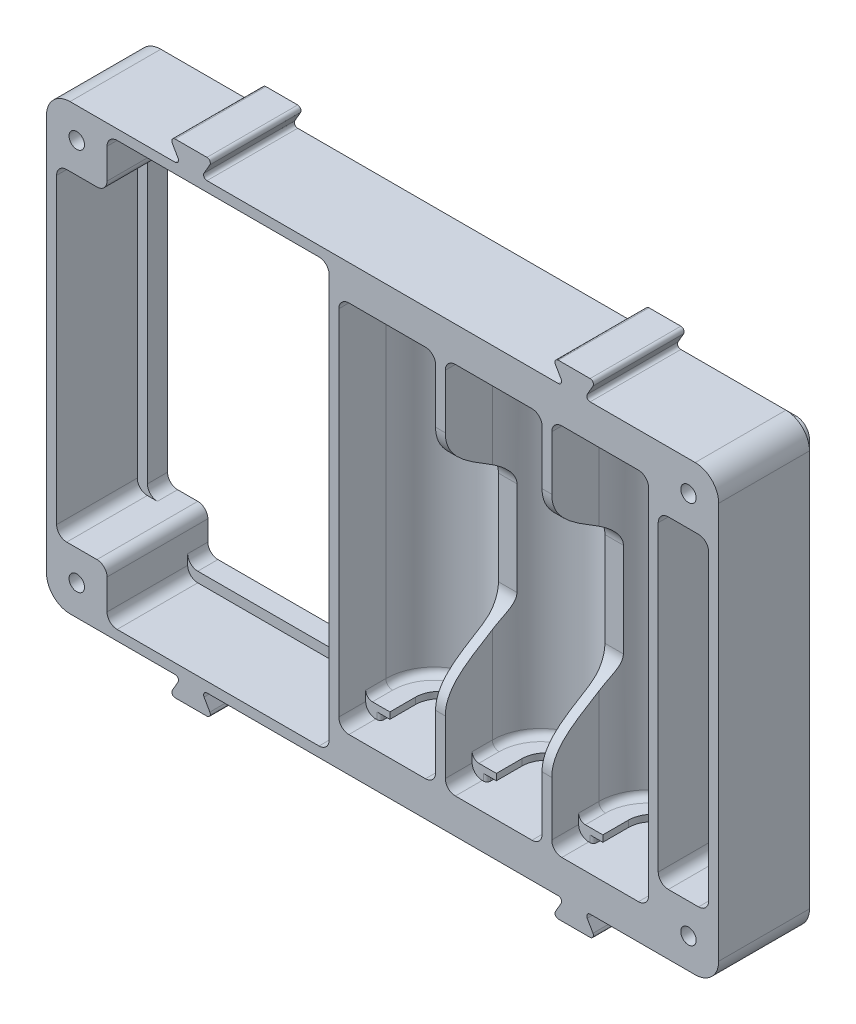
SolidWorks part; units mm, degrees
material "ABS"
ref_plane "Front Plane" through (0, 0, 0) normal (0, 0, 1) x (1, 0, 0)
ref_plane "Top Plane" through (0, 0, 0) normal (0, 1, 0) x (1, 0, 0)
ref_plane "Right Plane" through (0, 0, 0) normal (1, 0, 0) x (0, 0, -1)
sketch "Sketch1" plane through (0, 0, 0) normal (0, 1, 0) x (1, 0, 0)
  line L0 (-24.48, 0) -> (24.48, 0)
  line L1 (0, 0) -> (0, -8) construction
  line L2 (-5.4908, -0.8) -> (5.6475, -0.8) construction
  line L3 (7, -12.013) -> (7, -2.4204) construction
  line L4 (8.84, -11.8066) -> (8.84, -1.8587) construction
  line L5 (0, -8) -> (15.84, -8) construction
  line L6 (7.2, -8) -> (7.2, -15)
  line L7 (8.64, -8) -> (8.64, -15)
  line L8 (8.64, -15) -> (23.04, -15) construction
  line L9 (8.64, -15) -> (7.2, -15)
  line L10 (-1.7094, -15) -> (7.2, -15) construction
  line L11 (15.84, -8) -> (23.04, -8) construction
  line L12 (23.04, -15) -> (23.04, -8)
  line L13 (23.04, -15) -> (24.48, -15)
  line L14 (24.48, -15) -> (24.48, 0)
  line L15 (-24.48, -15) -> (-24.48, 0)
  line L16 (-23.04, -15) -> (-24.48, -15)
  line L17 (-23.04, -15) -> (-23.04, -8)
  line L18 (-8.64, -8) -> (-8.64, -15)
  line L19 (-8.64, -15) -> (-7.2, -15)
  line L20 (-7.2, -8) -> (-7.2, -15)
  circle A0 centre (0, -8) radius 7 construction
  arc A1 (-7.2, -8) -> (7.2, -8) centre (0, -8) cw
  circle A2 centre (15.84, -8) radius 7 construction
  arc A3 (8.64, -8) -> (23.04, -8) centre (15.84, -8) cw
  arc A4 (-8.64, -8) -> (-23.04, -8) centre (-15.84, -8) ccw
  dimension "D1" = 14
  dimension "D2" = 0.2
  dimension "D3" = 0.8
  dimension "D4" = 1.44
  dimension "D5" = 15
  dimension "D6" = 15.84
extrude "Boss-Extrude1" add sketch "Sketch1" along normal blind 27.8
sketch "Sketch2" plane through (0, 27.8, 0) normal (0, -1, 0) x (1, 0, 0)
  line L1 (-24.48, 15) -> (24.48, 15)
  line L2 (-24.48, 15) -> (-24.48, 0)
  line L3 (-24.48, 0) -> (24.48, 0)
  line L4 (24.48, 15) -> (24.48, 0)
extrude "Boss-Extrude2" add sketch "Sketch2" against normal blind 1.44
ref_plane "Plane1" through (-15.84, 0, 0) normal (1, 0, 0) x (0, 0, -1)
ref_plane "Plane3" through (15.84, 0, 0) normal (1, 0, 0) x (0, 0, -1)
sketch "Sketch6" plane through (0, 0, 0) normal (1, 0, 0) x (0, 0, -1)
  line L0 (-5, 0) -> (-15, 0)
  line L1 (-15, 0) -> (0, 0) construction
  line L2 (-15, 0) -> (-15, 18.24)
  line L3 (-15, 29.24) -> (-15, 0) construction
  line L4 (-5, 0) -> (-5, 7)
  line L5 (0, 29.24) -> (0, 0) construction
  line L6 (0, 29.24) -> (-15, 29.24) construction
  spline S0 degree 3 poles (-15, 18.24) (-15, 12.24) (-5, 11) (-5, 7) knots 0 0 0 0 1 1 1 1
  dimension "D4" = 12
  dimension "D5" = 18
  dimension "D1" = 7
  dimension "D2" = 5
  dimension "D3" = 11
extrude "Cut-Extrude2" cut sketch "Sketch6" against normal blind 15 and the other way blind 15
sketch "Sketch3" plane through (0, 27.8, 0) normal (0, -1, 0) x (1, 0, 0)
  line L0 (-10.34, 11) -> (-8.64, 11)
  line L1 (-8.64, 8) -> (-8.64, 15) construction
  line L2 (-8.64, 11) -> (-8.64, 0)
  line L3 (24.48, 0) -> (-24.48, 0) construction
  line L4 (-8.64, 0) -> (-23.04, 0)
  line L6 (-20.34, 2.9) -> (-11.34, 2.9)
  line L7 (-10.84, 3.4) -> (-10.84, 10.5)
  line L8 (-15.84, 15) -> (-15.84, 0) construction
  line L9 (-8.64, 15) -> (-23.04, 15) construction
  line L19 (-23.04, 11) -> (-23.04, 0)
  line L20 (-21.34, 11) -> (-23.04, 11)
  line L21 (-20.84, 3.4) -> (-20.84, 10.5)
  arc A1 (-11.34, 2.9) -> (-10.84, 3.4) centre (-11.34, 3.4) ccw
  arc A4 (-10.34, 11) -> (-10.84, 10.5) centre (-10.34, 10.5) ccw
  arc A6 (-20.34, 2.9) -> (-20.84, 3.4) centre (-20.34, 3.4) cw
  arc A7 (-21.34, 11) -> (-20.84, 10.5) centre (-21.34, 10.5) cw
  dimension "D6" = 0.5
  dimension "D7" = 0.5
  dimension "D1" = 5
  dimension "D2" = 11
  dimension "D3" = 2.9
extrude "Inner" add sketch "Sketch3" along normal blind 1
sketch "Sketch4" plane through (0, 26.8, 0) normal (0, -1, 0) x (1, 0, 0)
  line L1 (-8.64, 8) -> (-8.64, 15) construction
  line L2 (-8.64, 11) -> (-8.64, 0)
  line L3 (24.48, 0) -> (-24.48, 0) construction
  line L4 (-8.64, 0) -> (-23.04, 0)
  line L5 (-23.04, 0) -> (-23.04, 11)
  line L6 (-8.64, 11) -> (-10.34, 11) construction
  line L7 (-23.04, 11) -> (-19.44, 11)
  line L8 (-19.44, 11) -> (-19.44, 7.2)
  line L10 (-12.24, 7.2) -> (-12.24, 11)
  line L11 (-12.24, 11) -> (-8.64, 11)
  arc A0 (-19.44, 7.2) -> (-12.24, 7.2) centre (-15.84, 7.2) ccw
  dimension "D1" = 3.6
  dimension "D2" = 3.8
extrude "Boss-Extrude4" add sketch "Sketch4" along normal blind 0.96
sketch "Sketch5" plane through (0, 0, 15) normal (0, 0, 1) x (1, 0, 0)
  line L0 (-8.64, 27.8) -> (-23.04, 27.8) construction
  line L1 (-17.54, 27.8) -> (-14.14, 27.8)
  line L2 (-17.54, 27.8) -> (-17.54, 27.3)
  line L3 (-17.54, 27.3) -> (-14.14, 27.3)
  line L4 (-14.14, 27.8) -> (-14.14, 27.3)
  point P10 (-15.84, 27.8)
  dimension "D1" = 0.5
  dimension "D2" = 3.4
extrude "Cut-Extrude1" cut sketch "Sketch5" against normal through all
sketch "Sketch10" plane through (0, 0, 0) normal (0, 0, 1) x (1, 0, 0)
  line L0 (-24.48, 29.24) -> (24.48, 29.24) construction
  line L1 (-14.14, 27.3) -> (-17.54, 27.3)
  line L2 (-14.14, 27.3) -> (-14.14, 29.24)
  line L3 (-14.14, 29.24) -> (-17.54, 29.24)
  line L4 (-17.54, 27.3) -> (-17.54, 29.24)
extrude "Cut-Extrude6" cut sketch "Sketch10" along normal blind 0.6
mirror "Mirror1" about plane through (0, 0, 0) normal (1, 0, 0) of "Cut-Extrude6", "Inner", "Boss-Extrude4", "Cut-Extrude1"
ref_plane "Plane2" through (-7.92, 0, 0) normal (1, 0, 0) x (0, 0, -1)
mirror "Mirror2" about plane through (-7.92, 0, 0) normal (1, 0, 0) of "Cut-Extrude6", "Inner", "Boss-Extrude4", "Cut-Extrude1"
fillet "Fillet2" radius 1.5 6 edges at (-8.64, 27.8, 13) (-23.04, 27.8, 13) (23.04, 27.8, 13) (-7.2, 27.8, 13) (7.2, 27.8, 13) (8.64, 27.8, 13)
fillet "Fillet3" radius 1 9 edges at (-8.64, 25.84, 9.5) (-15.84, 25.84, 0.8) (-23.04, 25.84, 9.5) (23.04, 25.84, 9.5) (8.64, 25.84, 9.5) (7.2, 25.84, 9.5) (-7.2, 25.84, 9.5) (15.84, 25.84, 0.8) (0, 25.84, 0.8)
fillet "Fillet4" [suppressed] radius 2.94
mirror "Mirror4" about plane through (0, 0, 0) normal (0, 1, 0) of bodies 108 110
sketch "Sketch12" [suppressed] plane through (0, 0, 0) normal (0, 0, -1) x (-1, 0, 0)
  line L0 (-7.92, 7) -> (-7.92, 25) construction
  line L1 (-6.5452, 7) -> (-9.2948, 7) construction
  line L2 (7.92, 7) -> (7.92, 18) construction
  line L3 (9.2948, 7) -> (6.5452, 7) construction
  line L4 (7.92, 7) -> (7.92, -15) construction
  line L5 (-7.92, 7) -> (-7.92, -15) construction
  line L6 (0, 0) -> (-7.92, 0) construction
  circle A0 centre (-7.92, -15) radius 2.5 construction
  circle A1 centre (7.92, -15) radius 2.5 construction
  circle A2 centre (-7.92, 25) radius 2.5 construction
  circle A3 centre (7.92, 18) radius 2.5 construction
  dimension "D3" = 5
  dimension "D1" = 25
  dimension "D2" = 18
  dimension "D4" = 15
  dimension "D5" = 15
hole_wizard "Ø2.0mm Dowel Hole1" [suppressed] positions "Sketch13" profile "Sketch14" hole size "Ø2.0" standard "ANSI Metric"
sketch "Sketch13" [suppressed] plane through (0, 0, 0) normal (0, 0, -1) x (-1, 0, 0)
  point P0 (-7.92, 25)
  point P3 (7.92, 18)
  point P6 (7.92, -15)
  point P9 (-7.92, -15)
sketch "Sketch14" plane through (7.92, 25, 0) normal (1, 0, 0) x (0, 1, 0)
  line L0 (0, 0) -> (0, 5.5708)
  line L1 (0, 5.5708) -> (0.95, 5)
  line L2 (0.95, 5) -> (0.95, 0)
  line L5 (0.95, 0) -> (0, 0)
  line L10 (0, 5.5708) -> (-0.95, 5) construction
  line L11 (0, -6.35) -> (0, 107.95) construction
  dimension "Hole Dia." = 1.9
  dimension "Hole Depth" = 5
  dimension "Drill Angle" = 118
sketch "Эскиз1" plane through (0, 0, 0) normal (0, 0, -1) x (-1, 0, 0)
  line L0 (-24.48, 29.24) -> (-24.48, -29.24) construction
  line L5 (-33.48, 33) -> (66.52, 33)
  line L6 (-33.48, 33) -> (-33.48, -33)
  line L7 (-33.48, -33) -> (66.52, -33)
  line L8 (66.52, 33) -> (66.52, -33)
  line L9 (-33.48, 33) -> (66.52, -33) construction
  line L10 (-33.48, -33) -> (66.52, 33) construction
  line L11 (-31.98, -31.5) -> (65.02, -31.5)
  line L12 (-31.98, -31.5) -> (-31.98, 31.5)
  line L13 (-31.98, 31.5) -> (65.02, 31.5)
  line L14 (65.02, -31.5) -> (65.02, 31.5)
  line L15 (-31.98, -31.5) -> (65.02, 31.5) construction
  line L16 (-31.98, 31.5) -> (65.02, -31.5) construction
  line L17 (24.48, 29.24) -> (24.48, -29.24) construction
  line L18 (-24.48, 29.24) -> (24.48, 29.24)
  line L19 (-24.48, 29.24) -> (-24.48, 31.5)
  line L20 (-24.48, 31.5) -> (24.48, 31.5)
  line L21 (24.48, 29.24) -> (24.48, 31.5)
  line L22 (-24.48, -29.24) -> (24.48, -29.24)
  line L23 (-24.48, -29.24) -> (-24.48, -31.5)
  line L24 (-24.48, -31.5) -> (24.48, -31.5)
  line L25 (24.48, -29.24) -> (24.48, -31.5)
  line L27 (-24.48, 29.24) -> (-24.48, -29.24) construction
  line L28 (65.02, 31.5) -> (57.52, 31.5)
  line L29 (65.02, 31.5) -> (65.02, 24)
  line L30 (65.02, 24) -> (57.52, 24)
  line L31 (57.52, 31.5) -> (57.52, 24)
  line L32 (65.02, -31.5) -> (57.52, -31.5)
  line L33 (65.02, -31.5) -> (65.02, -24)
  line L34 (65.02, -24) -> (57.52, -24)
  line L35 (57.52, -31.5) -> (57.52, -24)
  line L36 (-31.98, 31.5) -> (-24.48, 31.5)
  line L37 (-31.98, 31.5) -> (-31.98, 24)
  line L38 (-31.98, 24) -> (-24.48, 24)
  line L39 (-24.48, 31.5) -> (-24.48, 24)
  line L41 (-31.98, -31.5) -> (-24.48, -31.5)
  line L42 (-31.98, -31.5) -> (-31.98, -24)
  line L43 (-31.98, -24) -> (-24.48, -24)
  line L44 (-24.48, -31.5) -> (-24.48, -24)
  point P0 (16.52, 0)
  point P5 (16.52, 0)
  line M16 (24.48, 29.24) -> (17.54, 29.24)
  line M20 (14.14, 29.24) -> (1.7, 29.24)
  line M24 (-1.7, 29.24) -> (-14.14, 29.24)
  line M28 (-17.54, 29.24) -> (-24.48, 29.24)
  line M30 (-24.48, 29.24) -> (-24.48, -29.24)
  dimension "D1" = 100
  dimension "D2" = 66
  dimension "D3" = 1.5
  dimension "D4" = 1.5
  dimension "D5" = 7.5
extrude "Бобышка-Вытянуть1" add sketch "Эскиз1" against normal blind 15 contours L13 L31 L30 L14 | L35 L11 L14 L34 | L43 L12 L11 L23 M30 | L12 L38 L19 L13 M30 | L8 L5 L6 L7 L14 L11 L12 L13 | L21 L13 L19 L18 M16 M28 M24 M20
sketch "Эскиз2" plane through (0, 0, 0) normal (0, 0, -1) x (-1, 0, 0)
  line L0 (65.02, -24) -> (65.02, 24) construction
  line L1 (-31.98, -31.5) -> (65.02, -31.5)
  line L2 (-31.98, -31.5) -> (-31.98, 31.5)
  line L3 (-31.98, 31.5) -> (65.02, 31.5)
  line L4 (65.02, -31.5) -> (65.02, 31.5)
  line L5 (-31.98, -24) -> (-31.98, 24) construction
  line L6 (24.48, 31.5) -> (57.52, 31.5) construction
  line L7 (24.48, -31.5) -> (57.52, -31.5) construction
  line L8 (-24.48, 24) -> (-24.48, -24) construction
  line L11 (-31.98, 24) -> (-24.48, 24)
  line L12 (-24.48, 31.5) -> (-24.48, 24)
  line L13 (57.52, 24) -> (65.02, 24)
  line L14 (57.52, 24) -> (57.52, 31.5)
  line L17 (57.52, -24) -> (65.02, -24)
  line L18 (57.52, -24) -> (57.52, -31.5)
  line L23 (-31.98, -24) -> (-24.48, -24)
  line L24 (-24.48, -31.5) -> (-24.48, -24)
  line L25 (-24.48, 30) -> (57.52, 30)
  line L26 (-24.48, -30) -> (57.52, -30)
  line L27 (-30.48, 24) -> (-30.48, -24)
  line L28 (63.52, -24) -> (63.52, 24)
  line L29 (65.02, 24) -> (57.52, 24) construction
  line M25 (-31.98, 24) -> (-24.48, 24)
  line M27 (-24.48, -24) -> (-31.98, -24)
  line M28 (-31.98, -24) -> (-31.98, 24)
  line M29 (24.48, -31.5) -> (24.48, 31.5)
  line M30 (24.48, 31.5) -> (57.52, 31.5)
  line M31 (57.52, 31.5) -> (57.52, 24)
  line M32 (57.52, 24) -> (65.02, 24)
  line M33 (65.02, 24) -> (65.02, -24)
  line M34 (65.02, -24) -> (57.52, -24)
  line M35 (57.52, -24) -> (57.52, -31.5)
  line M36 (57.52, -31.5) -> (24.48, -31.5)
  dimension "D1" = 1.5
  dimension "D2" = 1.5
  dimension "D3" = 1.5
  dimension "D4" = 1.5
extrude "Бобышка-Вытянуть2" add sketch "Эскиз2" against normal blind 3 contours L12 L3 L2 L11 M25 | L12 L25 L3 M29 | L25 M29 M31 M30 | L13 L4 L3 L14 M32 M31 | L28 L13 M34 M33 | L1 L4 L17 L18 M34 M35 | L26 L18 M29 M36 | L26 L24 L1 M29 | L1 L24 L23 L2 M27 | L27 L23 M25 M28
fillet "Скругление6" radius 3.5 4 edges at (33.48, 33, 7.5) (33.48, -33, 7.5) (-66.52, -33, 7.5) (-66.52, 33, 7.5)
sketch "Эскиз3" plane through (0, 0, 15) normal (0, 0, 1) x (1, 0, 0)
  line L0 (29.98, 33) -> (-63.02, 33) construction
  line L1 (-66.52, 29.5) -> (-66.52, -29.5) construction
  line L2 (33.48, 29.5) -> (33.48, -29.5) construction
  line L3 (29.98, -33) -> (-63.02, -33) construction
  point P0 (-62.02, 28.5)
  point P1 (28.98, 28.5)
  point P2 (28.98, -28.5)
  point P3 (-62.02, -28.5)
  dimension "D1" = 4.5
  dimension "D2" = 4.5
  dimension "D3" = 4.5
  dimension "D4" = 4.5
hole_wizard "Сверло под метчик  спиральное M2.22" positions "Эскиз4" profile "Эскиз5" hole size "M2.2x0.45" standard "DIN"
sketch "Эскиз4" plane through (0, 0, 15) normal (0, 0, 1) x (1, 0, 0)
  point P0 (-62.02, 28.5)
  point P3 (28.98, 28.5)
  point P6 (28.98, -28.5)
  point P9 (-62.02, -28.5)
sketch "Эскиз5" plane through (-62.02, 28.5, 15) normal (1, 0, 0) x (0, -1, 0)
  line L0 (0, 0) -> (0, 4.691)
  line L1 (0, 4.691) -> (1.15, 4)
  line L2 (1.15, 4) -> (1.15, 0)
  line L5 (1.15, 0) -> (0, 0)
  line L10 (0, 4.691) -> (-1.15, 4) construction
  line L11 (0, -6.35) -> (0, 107.95) construction
  dimension "Диаметр отверстия" = 2.3
  dimension "Глубина отверстия" = 4
  dimension "Угол заточки сверла" = 118
hole_wizard "Сверло под метчик  спиральное M2.23" [suppressed] positions "Эскиз6" profile "Эскиз7" hole size "M2.2x0.45" standard "DIN"
sketch "Эскиз6" plane through (0, 0, 1.5) normal (0, 0, 1) x (1, 0, 0)
  point P0 (28.98, 28.5)
  point P3 (28.98, -28.5)
  point P6 (-62.02, -28.5)
  point P9 (-62.02, 28.5)
sketch "Эскиз7" plane through (28.98, 28.5, 1.5) normal (1, 0, 0) x (0, -1, 0)
  line L0 (0, 0) -> (0, 4)
  line L1 (0, 4) -> (1.15, 3.309)
  line L2 (1.15, 3.309) -> (1.15, 0)
  line L5 (1.15, 0) -> (0, 0)
  line L10 (0, 4) -> (-1.15, 3.309) construction
  line L11 (0, -6.35) -> (0, 107.95) construction
  dimension "Диаметр отверстия" = 2.3
  dimension "Глубина отверстия" = 4
  dimension "Угол заточки сверла" = 118
sketch "Эскиз8" plane through (0, 0, 0) normal (0, 0, -1) x (-1, 0, 0)
  line L8 (65.02, -29.5) -> (65.02, 29.5)
  line L9 (-29.98, -31.5) -> (63.02, -31.5)
  line L10 (-31.98, 29.5) -> (-31.98, -29.5)
  line L11 (63.02, 31.5) -> (-29.98, 31.5)
  line L12 (65.02, -29.5) -> (65.02, 29.5)
  line L13 (-29.98, -31.5) -> (63.02, -31.5)
  line L14 (-31.98, 29.5) -> (-31.98, -29.5)
  line L15 (63.02, 31.5) -> (-29.98, 31.5)
  line L20 (66.52, -29.5) -> (66.52, 29.5)
  line L21 (-29.98, -33) -> (63.02, -33)
  line L22 (-33.48, 29.5) -> (-33.48, -29.5)
  line L23 (63.02, 33) -> (-29.98, 33)
  line L24 (66.52, -29.5) -> (66.52, 29.5)
  line L25 (-29.98, -33) -> (63.02, -33)
  line L26 (-33.48, 29.5) -> (-33.48, -29.5)
  line L27 (63.02, 33) -> (-29.98, 33)
  arc A8 (65.02, 29.5) -> (63.02, 31.5) centre (63.02, 29.5) ccw
  arc A9 (63.02, -31.5) -> (65.02, -29.5) centre (63.02, -29.5) ccw
  arc A10 (-31.98, -29.5) -> (-29.98, -31.5) centre (-29.98, -29.5) ccw
  arc A11 (-29.98, 31.5) -> (-31.98, 29.5) centre (-29.98, 29.5) ccw
  arc A12 (65.02, 29.5) -> (63.02, 31.5) centre (63.02, 29.5) ccw
  arc A13 (63.02, -31.5) -> (65.02, -29.5) centre (63.02, -29.5) ccw
  arc A14 (-31.98, -29.5) -> (-29.98, -31.5) centre (-29.98, -29.5) ccw
  arc A15 (-29.98, 31.5) -> (-31.98, 29.5) centre (-29.98, 29.5) ccw
  arc A20 (66.52, 29.5) -> (63.02, 33) centre (63.02, 29.5) ccw
  arc A21 (63.02, -33) -> (66.52, -29.5) centre (63.02, -29.5) ccw
  arc A22 (-33.48, -29.5) -> (-29.98, -33) centre (-29.98, -29.5) ccw
  arc A23 (-29.98, 33) -> (-33.48, 29.5) centre (-29.98, 29.5) ccw
  arc A24 (66.52, 29.5) -> (63.02, 33) centre (63.02, 29.5) ccw
  arc A25 (63.02, -33) -> (66.52, -29.5) centre (63.02, -29.5) ccw
  arc A26 (-33.48, -29.5) -> (-29.98, -33) centre (-29.98, -29.5) ccw
  arc A27 (-29.98, 33) -> (-33.48, 29.5) centre (-29.98, 29.5) ccw
  dimension "D1" = 1.5
  dimension "D2" = 0
extrude "Вырез-Вытянуть1" cut sketch "Эскиз8" against normal blind 1.5
hole_wizard "Сверло под метчик  спиральное M2.24" positions "Эскиз9" profile "Эскиз10" hole size "M2.2x0.45" standard "DIN"
sketch "Эскиз9" plane through (0, 0, 0) normal (0, 0, -1) x (-1, 0, 0)
  point P0 (-28.98, 28.5)
  point P3 (62.02, 28.5)
  point P6 (62.02, -28.5)
  point P9 (-28.98, -28.5)
sketch "Эскиз10" plane through (28.98, 28.5, 0) normal (1, 0, 0) x (0, 1, 0)
  line L0 (0, 0) -> (0, 4)
  line L1 (0, 4) -> (1.15, 3.309)
  line L2 (1.15, 3.309) -> (1.15, 0)
  line L5 (1.15, 0) -> (0, 0)
  line L10 (0, 4) -> (-1.15, 3.309) construction
  line L11 (0, -6.35) -> (0, 107.95) construction
  dimension "Диаметр отверстия" = 2.3
  dimension "Глубина отверстия" = 4
  dimension "Угол заточки сверла" = 118
fillet "Скругление7" radius 1.5 20 edges at (-24.48, -31.5, 9) (-24.48, -30, 1.5) (-57.52, -30, 1.5) (-57.52, -31.5, 9) (-57.52, -24, 7.5) (-24.48, 30, 1.5) (-24.48, 31.5, 9) (-57.52, 30, 1.5) (-57.52, 31.5, 9) (-57.52, 24, 7.5) (-63.52, 24, 1.5) (-65.02, 24, 9) (-63.52, -24, 1.5) (-65.02, -24, 9) (31.98, 24, 9) (31.98, -24, 9) (30.48, -24, 1.5) (24.48, -24, 7.5) (24.48, 24, 7.5) (30.48, 24, 1.5)
sketch "Эскиз11" plane through (0, 0, 15) normal (0, 0, 1) x (1, 0, 0)
  line L0 (-46.52, 33) -> (-48.2521, 36)
  line L1 (29.98, 33) -> (-63.02, 33) construction
  line L2 (-48.2521, 36) -> (-41.7879, 36)
  line L3 (-41.7879, 36) -> (-43.52, 33)
  line L4 (-43.52, 33) -> (-46.52, 33)
  line L5 (10.48, 33) -> (8.7479, 36)
  line L6 (8.7479, 36) -> (15.2121, 36)
  line L7 (15.2121, 36) -> (13.48, 33)
  line L8 (13.48, 33) -> (10.48, 33)
  line L9 (-66.52, 29.5) -> (-66.52, -29.5) construction
  line L10 (33.48, 29.5) -> (33.48, -29.5) construction
  line L11 (-46.52, -33) -> (-48.2521, -36)
  line L12 (29.98, -33) -> (-63.02, -33) construction
  line L13 (-48.2521, -36) -> (-41.7879, -36)
  line L14 (-41.7879, -36) -> (-43.52, -33)
  line L15 (-43.52, -33) -> (-46.52, -33)
  line L16 (10.48, -33) -> (8.7479, -36)
  line L17 (8.7479, -36) -> (15.2121, -36)
  line L18 (15.2121, -36) -> (13.48, -33)
  line L19 (13.48, -33) -> (10.48, -33)
  point P22 (0, 0)
  point P25 (-40.0361, -33)
  point P26 (0, 0)
  point P27 (0, 0)
  dimension "D1" = 60
  dimension "D2" = 3
  dimension "D3" = 3
  dimension "D4" = 3
  dimension "D5" = 20
  dimension "D6" = 20
  dimension "D7" = 3
extrude "Бобышка-Вытянуть3" add sketch "Эскиз11" against normal blind 13.5
fillet "Скругление8" radius 0.5 16 edges at (-48.2521, -36, 8.25) (-46.52, -33, 8.25) (-41.7879, -36, 8.25) (-43.52, -33, 8.25) (15.2121, -36, 8.25) (13.48, -33, 8.25) (8.7479, -36, 8.25) (10.48, -33, 8.25) (13.48, 33, 8.25) (15.2121, 36, 8.25) (10.48, 33, 8.25) (8.7479, 36, 8.25) (-46.52, 33, 8.25) (-43.52, 33, 8.25) (-41.7879, 36, 8.25) (-48.2521, 36, 8.25)
